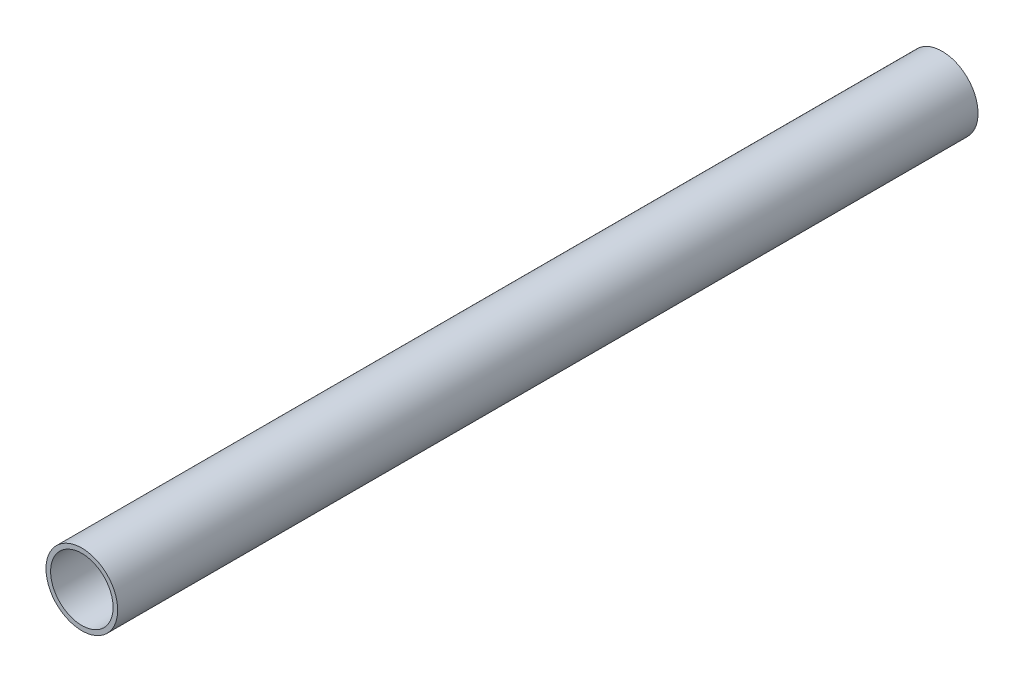
SolidWorks part; units mm, degrees
material "6061 Alloy"
ref_plane "Front Plane" through (0, 0, 0) normal (0, 0, 1) x (1, 0, 0)
ref_plane "Top Plane" through (0, 0, 0) normal (0, 1, 0) x (1, 0, 0)
ref_plane "Right Plane" through (0, 0, 0) normal (1, 0, 0) x (0, 0, -1)
sketch "Sketch1" plane through (0, 0, 0) normal (0, 0, 1) x (1, 0, 0)
  line L0 (-6.35, 0) -> (6.35, 0) construction
  line L1 (0, 0) -> (0, 1.0456) construction
  point P0 (-5.5372, 0)
  point P4 (0, 0)
  point P6 (5.5372, 0)
  dimension "OD" = 12.7
  dimension "ID" = 11.0744
sketch "Sketch2" plane through (0, 0, 0) normal (0, 0, 1) x (1, 0, 0)
  line L0 (-6.35, 0) -> (6.35, 0) construction
  circle A0 centre (0, 0) radius 5.5372
  circle A1 centre (0, 0) radius 6.35
  dimension "D1" = 11.0744
  dimension "D2" = 12.7
extrude "Boss-Extrude1" add sketch "Sketch2" along normal mid plane 152.4
sketch "Sketch3" plane through (0, 0, 0) normal (1, 0, 0) x (0, 0, -1)
  line L0 (76.2, 0) -> (-76.2, 0) construction
  line L1 (-76.2, 6.35) -> (-76.2, -6.35) construction
  line L2 (0, 0) -> (0, 21.8825) construction
  point P0 (-75.438, 0)
  point P6 (0, 0)
  point P8 (75.438, 0)
  dimension "D1" = 150.876
ref_axis "Center Axis 1" through (0, 0, 76.2) along (0, 0, -1)
ref_plane "Contact Plane 1" through (0, 0, 76.2) normal (0, 0, 1) x (1, 0, 0)
ref_plane "Contact Plane 2" through (0, 0, -76.2) normal (0, 0, -1) x (-1, 0, 0)
equation "\"D1@Sketch2\"=\"ID@Sketch1\""
equation "\"D2@Sketch2\"=\"OD@Sketch1\""
equation "\"D1@Sketch3\"=\"Length@Boss-Extrude1\"*0.99"
